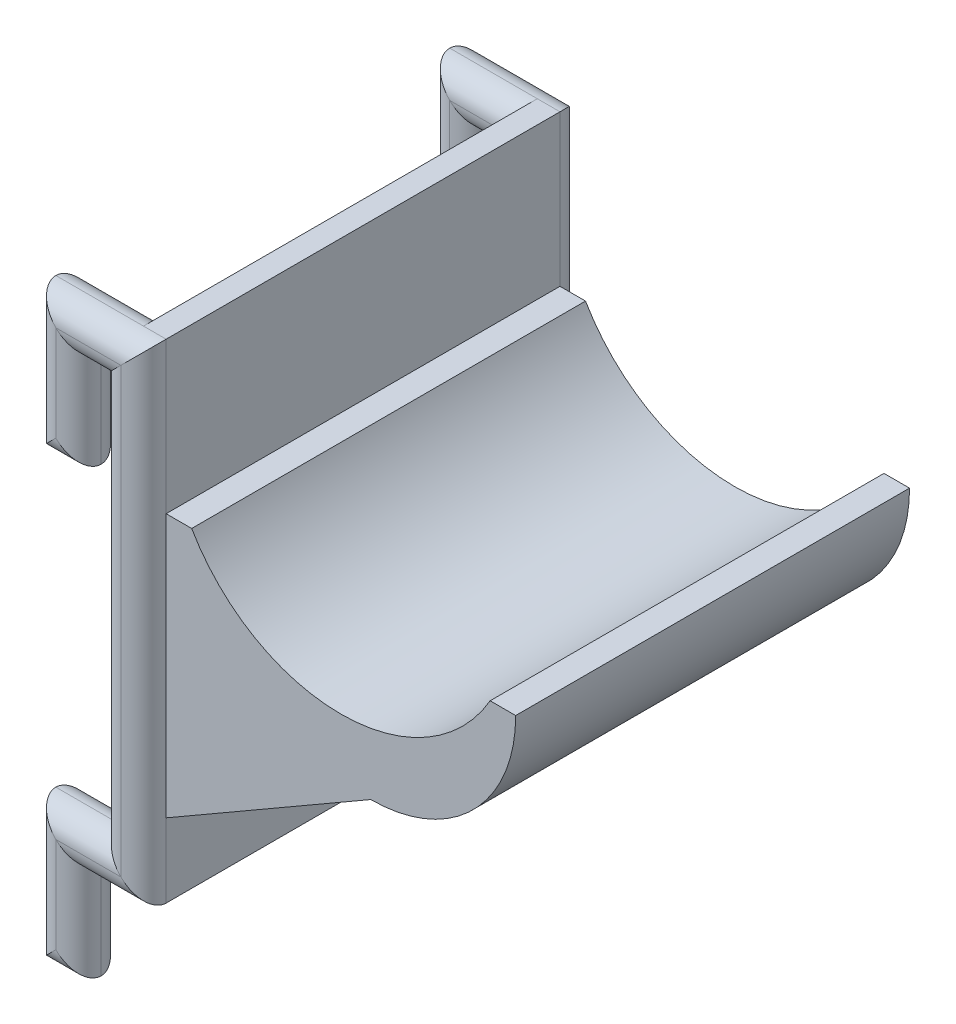
SolidWorks part; units mm, degrees
ref_plane "Plan de face" through (0, 0, 0) normal (0, 0, 1) x (1, 0, 0)
ref_plane "Plan de dessus" through (0, 0, 0) normal (0, 1, 0) x (1, 0, 0)
ref_plane "Plan de droite" through (0, 0, 0) normal (1, 0, 0) x (0, 0, -1)
sketch "Esquisse1" plane through (0, 0, 0) normal (0, 0, 1) x (1, 0, 0)
  line L0 (0, 0) -> (-6.6, 0)
  line L1 (-6.6, 0) -> (-6.6, -12)
  line L2 (0, 0) -> (0, -45)
  line L3 (0, -45) -> (-6.6, -45)
  line L4 (-6.6, -45) -> (-6.6, -57)
  dimension "D1" = 45
  dimension "D2" = 12
  dimension "D3" = 6.6
extrude "Extru.-Mince1" add sketch "Esquisse1" along normal mid plane 4.6 thin
fillet "Congé1" radius 2.3 24 edges at (-6.6, -57, -2.3) (-4.3, -52.15, -2.3) (-1, -47.3, -2.3) (2.3, -22.5, -2.3) (-3.3, 2.3, -2.3) (-8.9, -4.85, -2.3) (-6.6, -12, -2.3) (-4.3, -7.15, -2.3) (-3.3, -2.3, -2.3) (-2.3, -22.5, -2.3) (-5.6, -42.7, -2.3) (-8.9, -49.85, -2.3) (-5.6, -42.7, 2.3) (-2.3, -22.5, 2.3) (-3.3, -2.3, 2.3) (-4.3, -7.15, 2.3) (-6.6, -12, 2.3) (-8.9, -4.85, 2.3) (-3.3, 2.3, 2.3) (2.3, -22.5, 2.3) (-1, -47.3, 2.3) (-4.3, -52.15, 2.3) (-6.6, -57, 2.3) (-8.9, -49.85, 2.3)
sketch "Esquisse2" plane through (0, 0, 0) normal (1, 0, 0) x (0, 0, -1)
  line L1 (0, -47.3) -> (-40, -47.3)
  line L2 (0, -47.3) -> (0, 2.3)
  line L3 (0, 2.3) -> (-40, 2.3)
  line L4 (-40, -47.3) -> (-40, 2.3)
  dimension "D1" = 40
extrude "Boss.-Extru.1" add sketch "Esquisse2" along normal up to vertex (2.3 mm away) up to point (2.3, 2.3, 0)
pattern_linear "Répétition linéaire1" count 2 spacing 40 along (0, 0, 1) of "Extru.-Mince1"
fillet "Congé2" radius 2.3 23 edges at (-5.6, -42.7, 42.3) (-2.3, -22.5, 42.3) (-3.3, -2.3, 42.3) (-4.3, -7.15, 42.3) (-6.6, -12, 42.3) (-8.9, -4.85, 42.3) (-3.3, 2.3, 42.3) (2.3, -22.5, 42.3) (-6.6, -57, 42.3) (-4.3, -52.15, 42.3) (-1, -47.3, 42.3) (-8.9, -49.85, 42.3) (-2.15, -47.3, 37.7) (-4.3, -52.15, 37.7) (-6.6, -57, 37.7) (-8.9, -49.85, 37.7) (-5.6, -42.7, 37.7) (-2.3, -22.5, 37.7) (-3.3, -2.3, 37.7) (-4.3, -7.15, 37.7) (-6.6, -12, 37.7) (-8.9, -4.85, 37.7) (-4.45, 2.3, 37.7)
sketch "Esquisse3" plane through (0, 0, 0) normal (0, 0, 1) x (1, 0, 0)
  line L0 (2.3, 2.3) -> (2.3, -47.3) construction
  line L1 (23.0846, -27.8) -> (37.8, -27.8) construction
  line L2 (2.3, -39.8) -> (2.3, -13.05)
  line L3 (2.3, -13.05) -> (4.8946, -13.05)
  line L4 (37.8, -27.8) -> (37.8, -13.05) construction
  line L5 (20.05, -4.3) -> (20.05, -21.8) construction
  line L6 (23.0846, -27.8) -> (2.3, -39.8)
  line L7 (35.2054, -13.05) -> (37.8, -13.05)
  arc A0 (4.8946, -13.05) -> (35.2054, -13.05) centre (20.05, -4.3) ccw
  arc A1 (23.0846, -27.8) -> (37.8, -13.05) centre (23.0846, -13.0846) ccw
  point P8 (0, 0)
  point P9 (24.5284, -27.8)
  point P10 (37.8, -12.905)
  point P12 (23.05, -27.8)
  point P15 (0, 0)
  dimension "D1" = 35
  dimension "D2" = 7.5
  dimension "D3" = 14.75
  dimension "D4" = 60
  dimension "D5" = 35.5
  dimension "D6" = 12
  dimension "D7" = 8.75
extrude "Boss.-Extru.2" add sketch "Esquisse3" along normal blind 40
sketch "Esquisse4" plane through (0, 0, 0) normal (1, 0, 0) x (0, 0, -1)
  line L0 (-40, -39.8) -> (0, -39.8) construction
  line L1 (-35, -39.8) -> (-5, -39.8)
  line L2 (-35, -39.8) -> (-35, -27.8)
  line L3 (-35, -27.8) -> (-5, -27.8)
  line L4 (-5, -39.8) -> (-5, -27.8)
  line L6 (-20, -39.8) -> (-20, -13.05) construction
  line L7 (-40, -13.05) -> (0, -13.05) construction
  line L8 (-40, -39.8) -> (-40, -27.8) construction
  line L9 (-40, -27.8) -> (0, -27.8) construction
  point P6 (-5, -27.8)
  point P14 (0, 0)
  dimension "D1" = 5
extrude "Enlèv. mat.-Extru.1" cut sketch "Esquisse4" against normal up to surface (35.5 mm away) from vertex at 37.8 up to face at (2.3, -43.55, 20) starting at point (37.8, -13.05, 40)
